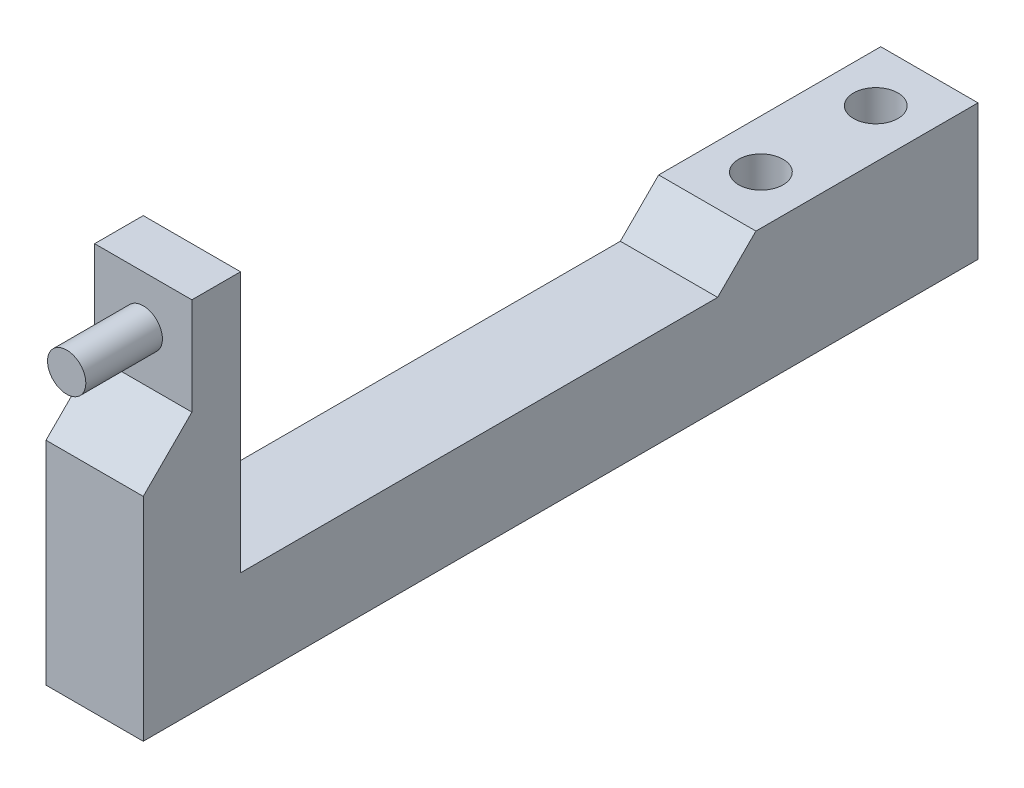
SolidWorks part; units mm, degrees
ref_plane "Front Plane" through (0, 0, 0) normal (0, 0, 1) x (1, 0, 0)
ref_plane "Top Plane" through (0, 0, 0) normal (0, 1, 0) x (1, 0, 0)
ref_plane "Right Plane" through (0, 0, 0) normal (1, 0, 0) x (0, 0, -1)
sketch "Sketch2" plane through (0, 0, 0) normal (0, 1, 0) x (1, 0, 0)
  line L1 (-6.35, -54.5) -> (6.35, -54.5)
  line L2 (-6.35, -54.5) -> (-6.35, 54.5)
  line L3 (-6.35, 54.5) -> (6.35, 54.5)
  line L4 (6.35, -54.5) -> (6.35, 54.5)
  line L5 (-6.35, -54.5) -> (6.35, 54.5) construction
  line L6 (-6.35, 54.5) -> (6.35, -54.5) construction
  point P0 (0, 0)
  dimension "D1" = 109
  dimension "D2" = 12.7
extrude "Boss-Extrude1" add sketch "Sketch2" along normal blind 12.7
sketch "Sketch5" plane through (0, 12.7, 0) normal (0, 1, 0) x (1, 0, 0)
  line L0 (6.35, 54.5) -> (-6.35, 54.5) construction
  line L2 (-6.35, 54.5) -> (6.35, 54.5)
  line L3 (-6.35, 54.5) -> (-6.35, 25.5)
  line L4 (-6.35, 25.5) -> (6.35, 25.5)
  line L5 (6.35, 54.5) -> (6.35, 25.5)
  point P7 (0, 25.5)
  dimension "D1" = 12.7
  dimension "D2" = 29
extrude "Boss-Extrude2" add sketch "Sketch5" along normal blind 5
hole_wizard "CBORE for M5 SHCS1" positions "Sketch3" profile "Sketch4" counterbore size "M5" standard "ANSI Metric" end condition through all
sketch "Sketch3" plane through (0, 0, 0) normal (0, -1, 0) x (-1, 0, 0)
  line L0 (0, 47.5) -> (0, 32.5) construction
  line L3 (-6.35, 54.5) -> (6.35, 54.5) construction
  point P0 (0, 47.5)
  point P2 (0, 32.5)
  dimension "D1" = 15
  dimension "D5" = 7
sketch "Sketch4" plane through (0, 0, -47.5) normal (1, 0, 0) x (0, 0, -1)
  line L0 (0, 0) -> (0, 17.7)
  line L1 (0, 17.7) -> (2.9, 17.7)
  line L3 (2.9, 17.7) -> (2.9, 5)
  line L4 (5, 5) -> (2.9, 5)
  line L5 (5, 5) -> (5, 0.021)
  line L6 (5, 0.021) -> (5.025, 0)
  line L7 (5.025, 0) -> (0, 0)
  line L8 (-5, 0.021) -> (-5.025, 0) construction
  line L11 (0, -6.35) -> (0, 107.95) construction
  dimension "Thru Hole Dia." = 5.8
  dimension "Thru Hole Depth" = 17.7
  dimension "C'Bore Dia." = 10
  dimension "C'Bore Depth" = 5
  dimension "Near C'Sink Dia." = 10.05
  dimension "Near C'Sink Angle" = 100
chamfer "Chamfer1" distance 5 angle 45 1 edges at (0, 12.7, -25.5)
sketch "Sketch7" plane through (0, 12.7, 0) normal (0, 1, 0) x (1, 0, 0)
  line L0 (6.35, -54.5) -> (6.35, 20.5) construction
  line L1 (-6.35, -54.5) -> (6.35, -54.5)
  line L2 (-6.35, -54.5) -> (-6.35, -41.8)
  line L3 (-6.35, -41.8) -> (6.35, -41.8)
  line L4 (6.35, -54.5) -> (6.35, -41.8)
  dimension "D1" = 12.7
extrude "Boss-Extrude4" add sketch "Sketch7" along normal blind 34.05
sketch "Sketch9" plane through (0, 0, 54.5) normal (0, 0, 1) x (1, 0, 0)
  line L0 (6.35, 46.75) -> (6.35, 0) construction
  line L1 (-6.35, 46.75) -> (6.35, 46.75)
  line L2 (-6.35, 46.75) -> (-6.35, 34.05)
  line L3 (-6.35, 34.05) -> (6.35, 34.05)
  line L4 (6.35, 46.75) -> (6.35, 34.05)
extrude "Cut-Extrude2" cut sketch "Sketch9" against normal offset from surface (6.35 mm away) 6.35 up to face at (0, 29.725, 41.8)
sketch "Sketch6" plane through (0, 0, 48.15) normal (0, 0, 1) x (1, 0, 0)
  line L0 (-6.35, 46.75) -> (6.35, 46.75) construction
  line L1 (6.35, 46.75) -> (6.35, 34.05) construction
  circle A0 centre (0, 40.4) radius 2.5
  point P2 (0, 40.7658)
  point P5 (0, 46.75)
  point P8 (6.35, 40.4)
  dimension "D1" = 5
extrude "Boss-Extrude7" add sketch "Sketch6" along normal blind 10 contours A0
chamfer "Chamfer3" distance 6.35 angle 45 1 edges at (0, 34.05, 54.5)
